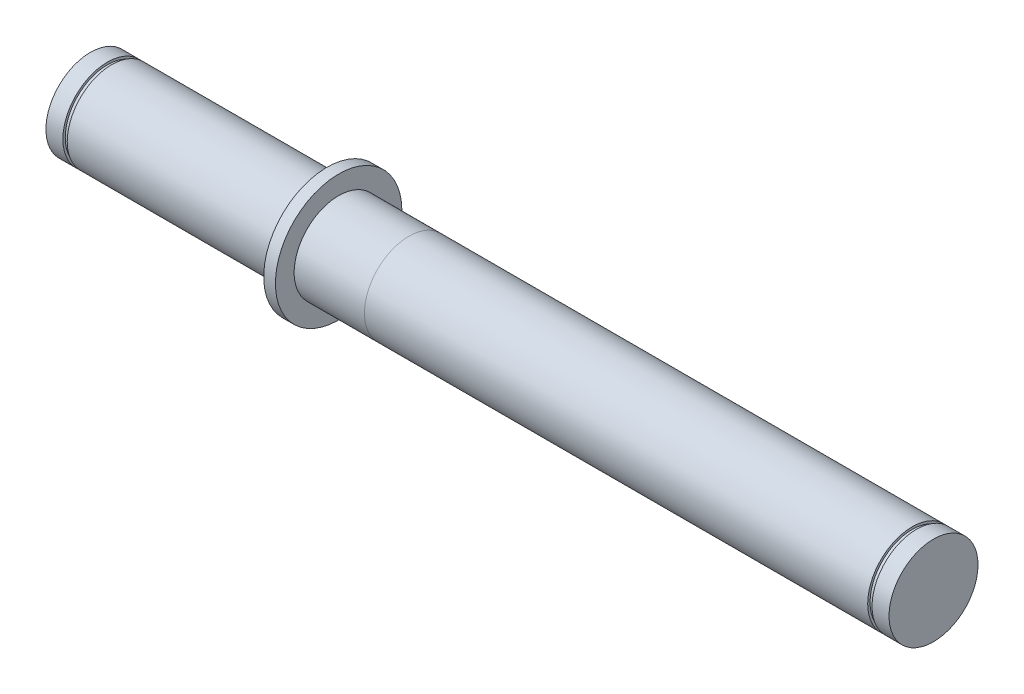
SolidWorks part; units mm, degrees
material "1.7225 (42CrMo4)"
ref_plane "E_Oben" through (0, 0, 0) normal (0, 0, 1) x (1, 0, 0)
ref_plane "E_Vorne" through (0, 0, 0) normal (0, 1, 0) x (1, 0, 0)
ref_plane "E_Rechts" through (0, 0, 0) normal (1, 0, 0) x (0, 0, -1)
ref_axis "A_Drehachse" through (-88.99, 0, 0) along (1, 0, 0)
sketch "Skizze1" plane through (0, 0, 0) normal (0, 0, 1) x (1, 0, 0)
  line L1 (0, -55) -> (0, 55) construction
  line L3 (180, 19) -> (180, 0)
  line L4 (180, 0) -> (-180, 0)
  line L5 (-44, 19.001) -> (-44, 19)
  line L6 (-44, 19.001) -> (-74, 19.001)
  line L7 (-180, 19) -> (-180, 0)
  line L10 (-79, 19) -> (-79, 27)
  line L11 (-79, 27) -> (-74, 27)
  line L12 (-74, 27) -> (-74, 19.001)
  line L14 (-180, 19) -> (-79, 19)
  line L17 (-44, 19) -> (180, 19)
  point P12 (0, 0)
  dimension "D1" = 101
  dimension "D2" = 19
  dimension "D3" = 19.001
  dimension "D4" = 180
  dimension "D5" = 27
  dimension "D6" = 30
  dimension "D7" = 5
revolve "Rotation1" add sketch "Skizze1" angle 360 about L4
sketch "Skizze19" plane through (0, 0, 0) normal (0, 0, 1) x (1, 0, 0)
  line L5 (-88.99, 0) -> (88.99, 0) construction
  line L8 (170.9, 19) -> (172.75, 19)
  line L9 (170.9, 19) -> (170.9, 18)
  line L10 (170.9, 18) -> (172.75, 18)
  line L11 (172.75, 19) -> (172.75, 18)
  line L14 (180, 19) -> (-44, 19) construction
  line L15 (180, -19) -> (180, 19) construction
  dimension "D1" = 7.25
  dimension "D2" = 0
  dimension "D4" = 1.85
  dimension "D5" = 18
revolve "Schnitt-Rotation1" cut sketch "Skizze19" angle 360 about axis through (-88.99, 0, 0) along (1, 0, 0)
sketch "Skizze20" plane through (0, 0, 0) normal (0, 0, 1) x (1, 0, 0)
  line L1 (-172.75, 19) -> (-170.9, 19)
  line L2 (-172.75, 19) -> (-172.75, 18)
  line L3 (-172.75, 18) -> (-170.9, 18)
  line L4 (-170.9, 19) -> (-170.9, 18)
  line L7 (-79, 19) -> (-180, 19) construction
  line L8 (-180, 19) -> (-180, -19) construction
  dimension "D1" = 7.25
  dimension "D2" = 1.85
  dimension "D3" = 1
  dimension "D4" = 0
revolve "Schnitt-Rotation2" cut sketch "Skizze20" angle 360 about axis through (-88.99, 0, 0) along (1, 0, 0)
